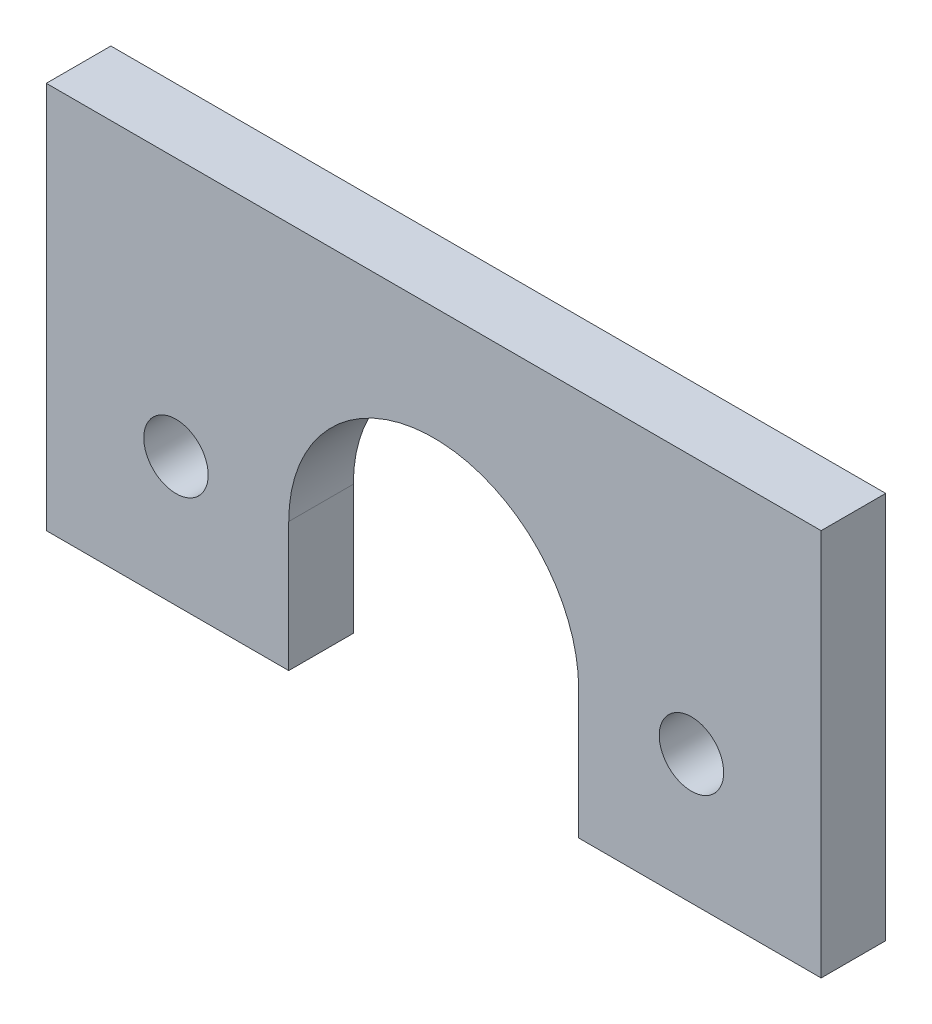
SolidWorks part; units mm, degrees
ref_plane "Front Plane" through (0, 0, 0) normal (0, 0, 1) x (1, 0, 0)
ref_plane "Top Plane" through (0, 0, 0) normal (0, 1, 0) x (1, 0, 0)
ref_plane "Right Plane" through (0, 0, 0) normal (1, 0, 0) x (0, 0, -1)
sketch "Sketch1" plane through (0, 0, 0) normal (0, 0, 1) x (1, 0, 0)
  line L0 (0, -25.0958) -> (0, 0.2498) construction
  line L1 (-14.2569, 0.2498) -> (-14.2569, 12.9226) construction
  line L2 (14.2569, 0.2498) -> (14.2569, 12.9226) construction
  line L3 (14.2569, 12.9226) -> (14.2569, 25.0958) construction
  line L4 (14.2569, 25.0958) -> (-14.2569, 25.0958) construction
  line L5 (-14.2569, 25.0958) -> (-14.2569, 12.9226) construction
  line L6 (0, 0.2498) -> (-25.3456, 0.2498) construction
  line L7 (-25.3456, 0.2498) -> (-25.3456, 12.9226) construction
  line L8 (-14.2569, 0.2498) -> (-14.2569, -12.4502)
  line L9 (-14.2569, -12.4502) -> (-38.1, -12.4502)
  line L10 (-38.1, -12.4502) -> (-38.1, 25.6498)
  line L11 (-38.1, 25.6498) -> (38.1, 25.6498)
  line L12 (0, 25.6498) -> (0, 0.2498) construction
  line L13 (14.2569, 0.2498) -> (14.2569, -12.4502)
  line L14 (14.2569, -12.4502) -> (38.1, -12.4502)
  line L15 (38.1, -12.4502) -> (38.1, 25.6498)
  circle A0 centre (0, 0.2498) radius 14.2569 construction
  circle A1 centre (-25.3456, 0.2498) radius 3.1682 construction
  circle A2 centre (25.3456, 0.2498) radius 3.1682 construction
  arc A3 (-14.2569, 0.2498) -> (14.2569, 0.2498) centre (0, 0.2498) cw
  circle A4 centre (-25.3456, 0.2498) radius 3.1682
  circle A5 centre (25.3456, 0.2498) radius 3.1682
  dimension "D1" = 38.1
  dimension "D2" = 38.1
  dimension "D3" = 25.4
extrude "Boss-Extrude1" add sketch "Sketch1" along normal blind 6.35 contours L8 A3 L13 L14 L15 L11 L10 L9 A4 A5 region at (-15.1088, -6.1002, 0)
